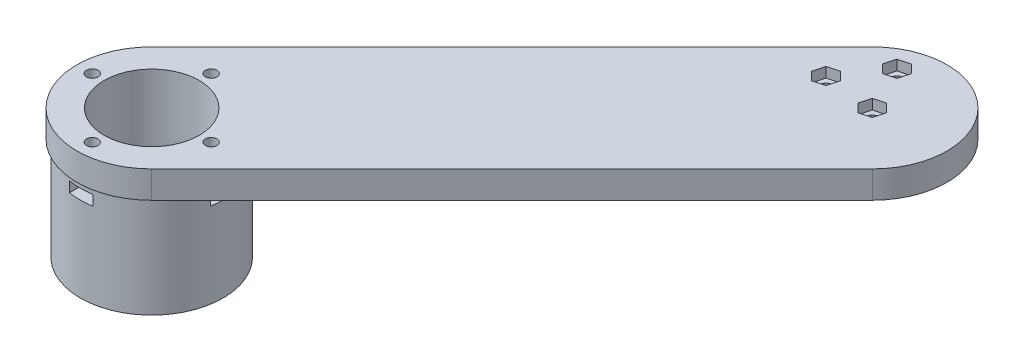
SolidWorks part; units mm, degrees
ref_plane "Front Plane" through (0, 0, 0) normal (0, 0, 1) x (1, 0, 0)
ref_plane "Top Plane" through (0, 0, 0) normal (0, 1, 0) x (1, 0, 0)
ref_plane "Right Plane" through (0, 0, 0) normal (1, 0, 0) x (0, 0, -1)
sketch "Sketch1" plane through (0, 0, 0) normal (0, 1, 0) x (1, 0, 0)
  line L0 (0, 0) -> (106.066, 106.066) construction
  line L1 (3.4641, 17.5) -> (1.7321, 20.5)
  line L2 (1.7321, 20.5) -> (-1.7321, 20.5)
  line L3 (-1.7321, 20.5) -> (-3.4641, 17.5)
  line L4 (-3.4641, 17.5) -> (-1.7321, 14.5)
  line L5 (-1.7321, 14.5) -> (1.7321, 14.5)
  line L6 (1.7321, 14.5) -> (3.4641, 17.5)
  line L7 (-17.5, -3.4641) -> (-14.5, -1.7321)
  line L8 (-14.5, -1.7321) -> (-14.5, 1.7321)
  line L9 (-14.5, 1.7321) -> (-17.5, 3.4641)
  line L10 (-17.5, 3.4641) -> (-20.5, 1.7321)
  line L11 (-20.5, 1.7321) -> (-20.5, -1.7321)
  line L12 (-20.5, -1.7321) -> (-17.5, -3.4641)
  line L13 (-3.4641, -17.5) -> (-1.7321, -20.5)
  line L14 (-1.7321, -20.5) -> (1.7321, -20.5)
  line L15 (1.7321, -20.5) -> (3.4641, -17.5)
  line L16 (3.4641, -17.5) -> (1.7321, -14.5)
  line L17 (1.7321, -14.5) -> (-1.7321, -14.5)
  line L18 (-1.7321, -14.5) -> (-3.4641, -17.5)
  line L19 (17.5, 3.4641) -> (14.5, 1.7321)
  line L20 (14.5, 1.7321) -> (14.5, -1.7321)
  line L21 (14.5, -1.7321) -> (17.5, -3.4641)
  line L22 (17.5, -3.4641) -> (20.5, -1.7321)
  line L23 (20.5, -1.7321) -> (20.5, 1.7321)
  line L24 (20.5, 1.7321) -> (17.5, 3.4641)
  line L25 (-15.5563, 15.5563) -> (90.5097, 121.6224)
  line L26 (15.5563, -15.5563) -> (121.6224, 90.5097)
  line L27 (106.066, 106.066) -> (-1.0853, 181.0942) construction
  line L28 (97.4624, 93.7787) -> (-9.689, 168.8069)
  line L29 (114.6697, 118.3533) -> (7.5183, 193.3815)
  line L30 (99.7189, 119.6662) -> (91.1152, 107.3789) construction
  line L31 (106.9626, 109.4121) -> (103.6165, 108.5155)
  line L32 (103.6165, 108.5155) -> (102.72, 105.1694)
  line L33 (102.72, 105.1694) -> (105.1694, 102.72)
  line L34 (105.1694, 102.72) -> (108.5155, 103.6165)
  line L35 (108.5155, 103.6165) -> (109.4121, 106.9626)
  line L36 (109.4121, 106.9626) -> (106.9626, 109.4121)
  line L37 (97.2329, 93.4511) -> (-9.9184, 168.4793)
  line L38 (90.2186, 104.0328) -> (93.5647, 104.9294)
  line L39 (93.5647, 104.9294) -> (94.4613, 108.2754)
  line L40 (94.4613, 108.2754) -> (92.0118, 110.7249)
  line L41 (92.0118, 110.7249) -> (88.6657, 109.8284)
  line L42 (88.6657, 109.8284) -> (87.7692, 106.4823)
  line L43 (87.7692, 106.4823) -> (90.2186, 104.0328)
  line L44 (100.6154, 123.0122) -> (97.2694, 122.1156)
  line L45 (97.2694, 122.1156) -> (96.3728, 118.7696)
  line L46 (96.3728, 118.7696) -> (98.8223, 116.3201)
  line L47 (98.8223, 116.3201) -> (102.1684, 117.2167)
  line L48 (102.1684, 117.2167) -> (103.0649, 120.5627)
  line L49 (103.0649, 120.5627) -> (100.6154, 123.0122)
  line L50 (-3.4641, 17.5) -> (3.4641, 17.5)
  line L51 (-3.4641, 17.5) -> (-3.4641, 23.8539)
  line L52 (-3.4641, 23.8539) -> (3.4641, 23.8539)
  line L53 (3.4641, 17.5) -> (3.4641, 23.8539)
  line L54 (-17.5, -3.4641) -> (-25.5814, -3.4641)
  line L55 (-17.5, -3.4641) -> (-17.5, 3.4641)
  line L56 (-17.5, 3.4641) -> (-25.5814, 3.4641)
  line L57 (-25.5814, -3.4641) -> (-25.5814, 3.4641)
  line L58 (-3.4641, -17.5) -> (3.4641, -17.5)
  line L59 (-3.4641, -17.5) -> (-3.4641, -25.8241)
  line L60 (-3.4641, -25.8241) -> (3.4641, -25.8241)
  line L61 (3.4641, -17.5) -> (3.4641, -25.8241)
  line L62 (17.5, 3.4641) -> (24.0978, 3.4641)
  line L63 (17.5, 3.4641) -> (17.5, -3.4641)
  line L64 (17.5, -3.4641) -> (24.0978, -3.4641)
  line L65 (24.0978, 3.4641) -> (24.0978, -3.4641)
  line L66 (114.8991, 118.681) -> (7.7477, 193.7091)
  circle A0 centre (0, 0) radius 14
  circle A1 centre (0, 0) radius 21
  circle A2 centre (0, 0) radius 17.5 construction
  circle A3 centre (0, 17.5) radius 1.7
  circle A4 centre (17.5, 0) radius 1.7
  circle A5 centre (0, -17.5) radius 1.7
  circle A6 centre (-17.5, 0) radius 1.7
  circle A7 centre (0, 17.5) radius 3 construction
  circle A8 centre (-17.5, 0) radius 3 construction
  circle A9 centre (0, -17.5) radius 3 construction
  circle A10 centre (17.5, 0) radius 3 construction
  arc A12 (-15.5563, 15.5563) -> (15.5563, -15.5563) centre (0, 0) ccw
  arc A13 (121.6224, 90.5097) -> (90.5097, 121.6224) centre (106.066, 106.066) ccw
  arc A14 (97.4624, 93.7787) -> (114.6697, 118.3533) centre (106.066, 106.066) ccw
  arc A15 (7.5183, 193.3815) -> (-9.689, 168.8069) centre (-1.0853, 181.0942) ccw
  circle A16 centre (106.066, 106.066) radius 1.7
  circle A17 centre (106.066, 106.066) radius 3 construction
  circle A18 centre (99.7189, 119.6662) radius 1.7
  circle A19 centre (91.1152, 107.3789) radius 1.7
  circle A20 centre (91.1152, 107.3789) radius 3 construction
  circle A21 centre (99.7189, 119.6662) radius 3 construction
  arc A22 (7.7477, 193.7091) -> (-9.9184, 168.4793) centre (-1.0853, 181.0942) ccw
  arc A23 (97.2329, 93.4511) -> (114.8991, 118.681) centre (106.066, 106.066) ccw
  point P14 (53.033, 53.033)
  point P50 (52.4903, 143.5801)
  point P66 (95.417, 113.5225)
  dimension "D1" = 28
  dimension "D2" = 42
  dimension "D4" = 3.4
  dimension "D5" = 3.4
  dimension "D6" = 3.4
  dimension "D7" = 3.4
  dimension "D8" = 6
  dimension "D3" = 3.5
  dimension "D9" = 3.5
  dimension "D10" = 6
  dimension "D11" = 6
  dimension "D12" = 6
  dimension "D13" = 22
  dimension "D17" = 15
  dimension "D18" = 3.4
  dimension "D19" = 6
  dimension "D20" = 3.4
  dimension "D22" = 3.4
  dimension "D23" = 6
  dimension "D24" = 6
  dimension "D14" = 45
  dimension "D15" = 150
  dimension "D16" = 80
  dimension "D21" = 15
  dimension "D25" = 13
  dimension "D26" = 0.4
extrude "Boss-Extrude1" add sketch "Sketch1" along normal blind 8 contours L26 A13 L25 A12
extrude "Boss-Extrude2" add sketch "Sketch1<4>" against normal blind 30 contours A1 | A0
sketch "Sketch1<4>" plane through (0, 0, 0) normal (0, 1, 0) x (1, 0, 0) same geometry as "Sketch1"
extrude "Cut-Extrude3" cut sketch "Sketch1<6>" along normal blind 3 from offset 5 contours A1 L53 L52 L51 | L53 A1 L51 L3 L2 L1 | A3 L50 L4 L5 L6 | A3 L50 L1 L2 L3 | A4 L63 L19 L20 L21 | A4 L63 L22 L23 L24 | A1 L64 L65 L62 | L64 A1 L62 L24 L23 L22 | A12 L59 L60 L61 | L59 A1 L61 L15 L14 L13 | L59 A12 L61 A1 | A5 L58 L13 L14 L15 | A5 L58 L16 L17 L18 | A6 L55 L7 L8 L9 | A6 L55 L10 L11 L12 | L56 A1 L54 L12 L11 L10 | L56 A12 L54 A1 | A12 L56 L57 L54 region at (2.5821, 0, -17.5755) region at (2.5327, 0, -16.0377) region at (2.6653, 0, -19.0388) region at (0, 0, -22.3779) region at (20.8506, 0, -1.7316) region at (22.4999, 0, 0) region at (17.4245, 0, -2.5821) region at (18.9623, 0, -2.5327) region at (-21.4062, 0, 0) region at (-19.1062, 0, -3.3865) region at (-17.5755, 0, -2.5821) region at (-16.0377, 0, -2.5327) region at (-23.7442, 0, 0) region at (0, 0, 20.9224) region at (0, 0, 21.4062) region at (2.5821, 0, 17.4245) region at (2.5327, 0, 18.9623) region at (0, 0, 23.8656) offset against normal yes
sketch "Sketch1<6>" plane through (0, 0, 0) normal (0, 1, 0) x (1, 0, 0) same geometry as "Sketch1"
extrude "Cut-Extrude4" cut sketch "Sketch1<7>" along normal blind 1 from surface contours A3 L50 L4 L5 L6 | A3 L50 L1 L2 L3 | A6 L55 L7 L8 L9 | A6 L55 L10 L11 L12 | A4 L63 L22 L23 L24 | A4 L63 L19 L20 L21 | A5 L58 L16 L17 L18 | A5 L58 L13 L14 L15 region at (2.5821, 0, -17.5755) region at (2.5327, 0, -16.0377) region at (17.4245, 0, -2.5821) region at (18.9623, 0, -2.5327) region at (-17.5755, 0, -2.5821) region at (-16.0377, 0, -2.5327) region at (2.5821, 0, 17.4245) region at (2.5327, 0, 18.9623) starting at face at (-17.6187, -2, 0)
sketch "Sketch1<7>" plane through (0, 0, 0) normal (0, 1, 0) x (1, 0, 0) same geometry as "Sketch1"
extrude "Cut-Extrude2" cut sketch "Sketch1<3>" along normal through all and the other way up to surface (5 mm away) contours A0 | A3 | A6 | A4 | A5 | A18 | A16 | A19 other way up to face at (-17.5, -5, 1.7)
sketch "Sketch1<3>" plane through (0, 0, 0) normal (0, 1, 0) x (1, 0, 0) same geometry as "Sketch1"
extrude "Cut-Extrude5" cut sketch "Sketch1<8>" against normal blind 3 from surface contours L48 L49 L44 L45 L46 L47 A18 | L42 L43 L38 L39 L40 L41 A19 | L35 L36 L31 L32 L33 L34 A16 region at (108.1204, 0, -108.1204) region at (89.0608, 0, -105.3245) region at (101.7733, 0, -121.7206) starting at face at (91.1152, 8, -105.6789)
sketch "Sketch1<8>" plane through (0, 0, 0) normal (0, 1, 0) x (1, 0, 0) same geometry as "Sketch1"
extrude "Cut-Extrude6" cut sketch "Sketch1<9>" along normal blind 3 from surface contours L66 A22 L37 A23 starting at face at (91.1152, 0, -105.6789)
sketch "Sketch1<9>" plane through (0, 0, 0) normal (0, 1, 0) x (1, 0, 0) same geometry as "Sketch1"
